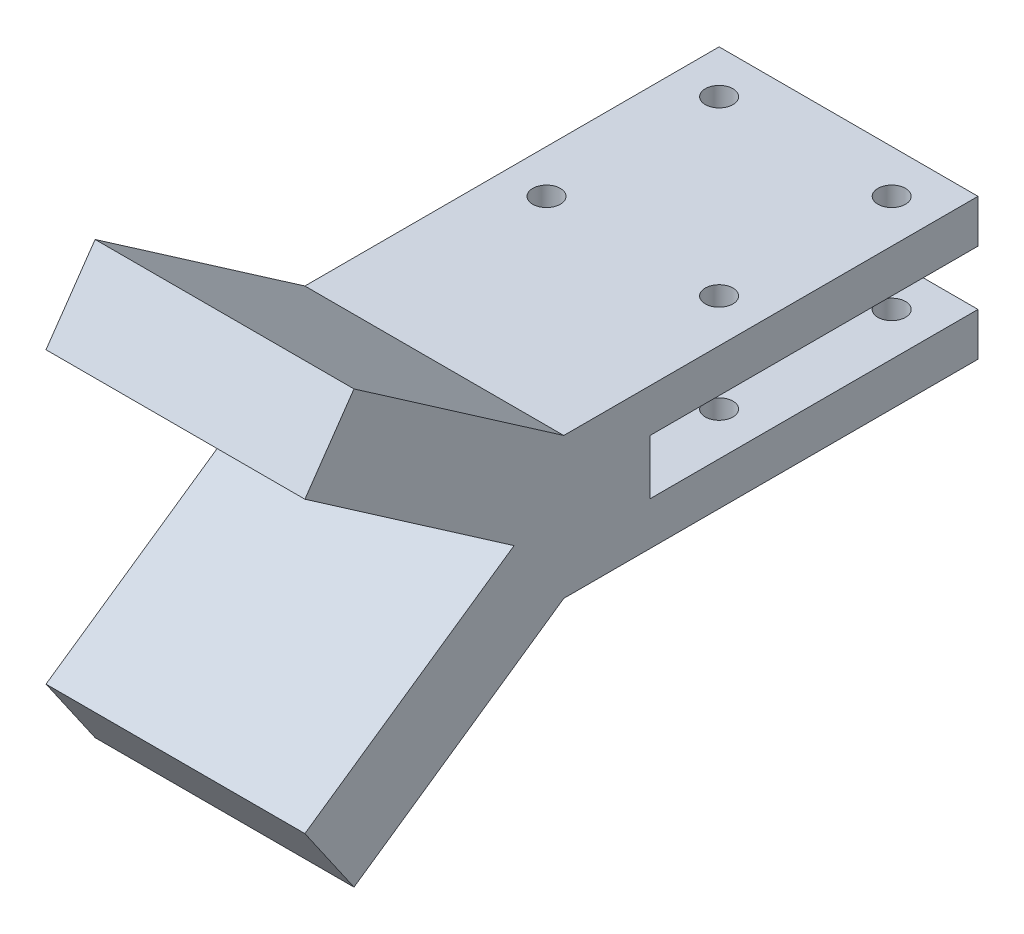
SolidWorks part; units mm, degrees
ref_plane "Front Plane" through (0, 0, 0) normal (0, 0, 1) x (1, 0, 0)
ref_plane "Top Plane" through (0, 0, 0) normal (0, 1, 0) x (1, 0, 0)
ref_plane "Right Plane" through (0, 0, 0) normal (1, 0, 0) x (0, 0, -1)
sketch "Sketch1" plane through (0, 0, 0) normal (1, 0, 0) x (0, 0, -1)
  line L0 (0, 0) -> (0, 23.7212) construction
  line L1 (0, 0) -> (43.6302, 0) construction
  line L2 (0, -3.175) -> (38, -3.175)
  line L3 (38, 3.175) -> (38, 8.175)
  line L4 (38, 8.175) -> (-10, 8.175)
  line L5 (-10, 8.175) -> (-34.3089, 25)
  line L6 (-34.3089, 25) -> (-40, 16.7774)
  line L7 (-40, 16.7774) -> (-15.7599, 0)
  line L8 (0, -3.175) -> (0, 3.175)
  line L9 (0, 3.175) -> (38, 3.175)
  line L10 (-40, -16.7774) -> (-15.7599, 0)
  line L11 (-34.3089, -25) -> (-40, -16.7774)
  line L12 (-10, -8.175) -> (-34.3089, -25)
  line L13 (38, -8.175) -> (-10, -8.175)
  line L14 (38, -3.175) -> (38, -8.175)
  point P18 (-15.1445, 0)
  point P19 (34.3025, 8.175)
  point P20 (-26.6825, 25)
  point P21 (-31.4846, 25)
  point P22 (0, 0)
  dimension "D1" = 10
  dimension "D2" = 5
  dimension "D3" = 6.35
  dimension "D4" = 50
  dimension "D5" = 10
  dimension "D6" = 40
  dimension "D7" = 38
extrude "Boss-Extrude1" add sketch "Sketch1" along normal blind 30
hole_wizard "M3 Clearance Hole1" positions "Sketch2" profile "Sketch3" hole size "M3" standard "ANSI Metric" end condition through all
sketch "Sketch2" plane through (0, 8.175, 0) normal (0, 1, 0) x (1, 0, 0)
  line L1 (15, 38) -> (15, -8.9474) construction
  line L2 (30, 38) -> (0, 38) construction
  line L4 (0, 23) -> (37.2003, 23) construction
  line L5 (0, 38) -> (0, -10) construction
  point P0 (5, 33)
  point P23 (25, 33)
  point P24 (25, 13)
  point P25 (5, 13)
  dimension "D1" = 10
  dimension "D2" = 10
  dimension "D3" = 15
sketch "Sketch3" plane through (5, 8.175, -33) normal (1, 0, 0) x (0, 0, 1)
  line L0 (0, 0) -> (0, 33.175)
  line L1 (0, 33.175) -> (1.6, 33.175)
  line L2 (1.6, 33.175) -> (1.6, 0)
  line L5 (1.6, 0) -> (0, 0)
  line L11 (0, -6.35) -> (0, 107.95) construction
  dimension "Thru Hole Dia." = 3.2
  dimension "Thru Hole Depth" = 33.175
